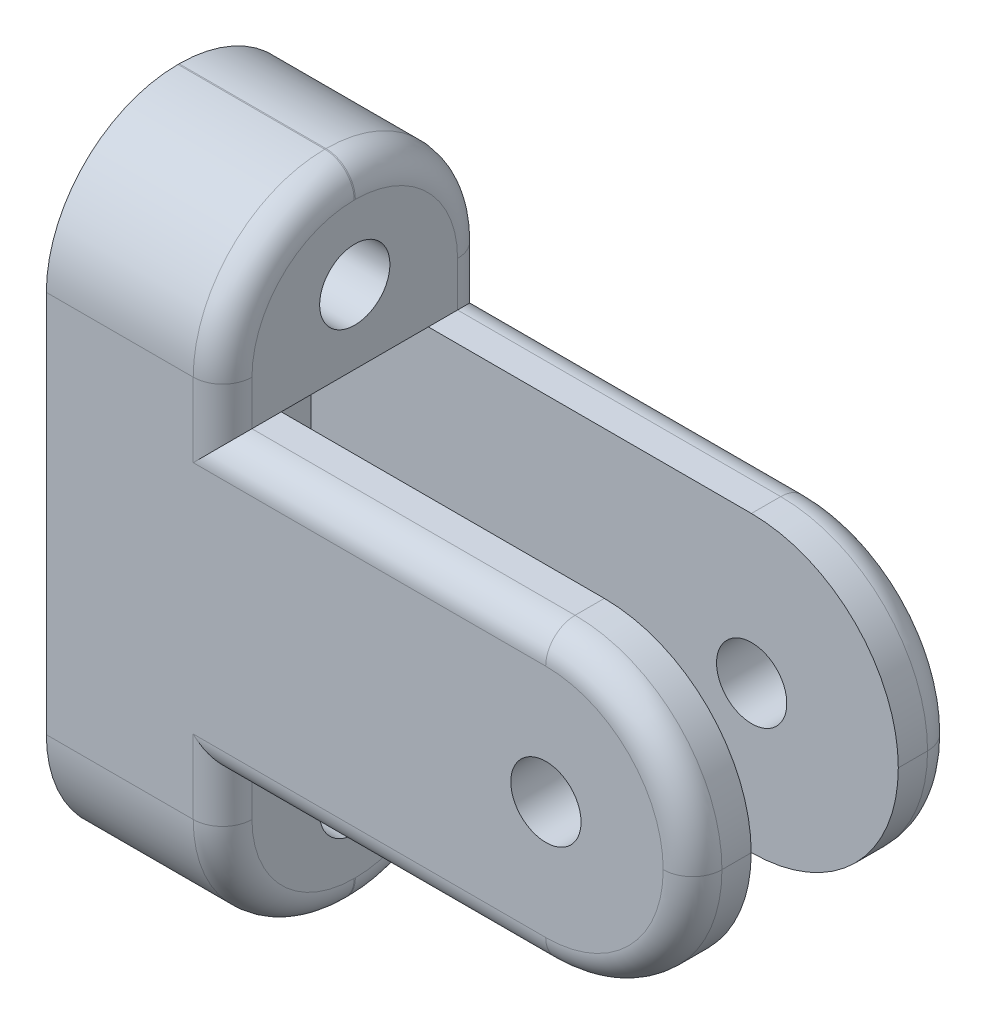
SolidWorks part; units mm, degrees
ref_plane "Front Plane" through (0, 0, 0) normal (0, 0, 1) x (1, 0, 0)
ref_plane "Top Plane" through (0, 0, 0) normal (0, 1, 0) x (1, 0, 0)
ref_plane "Right Plane" through (0, 0, 0) normal (1, 0, 0) x (0, 0, -1)
sketch "Sketch1" plane through (0, 0, 0) normal (1, 0, 0) x (0, 0, -1)
  line L1 (0, 0) -> (14.2875, 0)
  line L2 (0, 0) -> (0, 15.875)
  line L3 (0, 15.875) -> (14.2875, 15.875)
  line L4 (14.2875, 0) -> (14.2875, 15.875)
  dimension "D1" = 14.2875
  dimension "D2" = 15.875
extrude "Boss-Extrude1" add sketch "Sketch1" along normal blind 34.925
sketch "Sketch2" plane through (34.925, 0, 0) normal (1, 0, 0) x (0, 0, -1)
  line L0 (0, 15.875) -> (14.2875, 0) construction
  line L1 (14.2875, 0) -> (14.2875, 15.875) construction
  line L2 (0, 0) -> (14.2875, 0) construction
  line L4 (3.1687, 0) -> (11.1189, 0)
  line L5 (14.2875, 15.875) -> (0, 0) construction
  line L6 (3.1687, 0) -> (3.1687, 15.875)
  line L7 (3.1687, 15.875) -> (11.1189, 15.875)
  line L8 (11.1189, 0) -> (11.1189, 15.875)
  line L9 (3.1687, 0) -> (11.1189, 15.875) construction
  line L10 (3.1687, 15.875) -> (11.1189, 0) construction
  point P7 (7.1438, 7.9375)
  dimension "D1" = 15.875
  dimension "D2" = 7.9502
extrude "Cut-Extrude1" cut sketch "Sketch2" against normal blind 31.75
hole_wizard "#6 Clearance Hole1" positions "Sketch3" profile "Sketch4" hole size "#6" standard "ANSI Inch" end condition through all
sketch "Sketch3" plane through (0, 0, -14.2875) normal (0, 0, -1) x (-1, 0, 0)
  line L1 (-34.925, 7.9375) -> (0, 7.9375) construction
  line L2 (-34.925, 0) -> (-34.925, 15.875) construction
  line L3 (0, 0) -> (0, 15.875) construction
  point P0 (-27.0002, 7.9375)
  dimension "D1" = 27.0002
sketch "Sketch4" plane through (27.0002, 7.9375, -14.2875) normal (1, 0, 0) x (0, 1, 0)
  line L0 (0, 0) -> (0, 14.2875)
  line L1 (0, 14.2875) -> (1.8986, 14.2875)
  line L2 (1.8986, 14.2875) -> (1.8986, 0)
  line L5 (1.8986, 0) -> (0, 0)
  line L11 (0, -6.35) -> (0, 107.95) construction
  dimension "Thru Hole Dia." = 3.7973
  dimension "Thru Hole Depth" = 14.2875
sketch "Sketch5" plane through (0, 0, 0) normal (-1, 0, 0) x (0, 0, 1)
  line L0 (0, 15.875) -> (0, 0) construction
  line L1 (-14.2875, 15.875) -> (0, 15.875)
  line L2 (-14.2875, 15.875) -> (-14.2875, 25.4)
  line L3 (-14.2875, 25.4) -> (0, 25.4)
  line L4 (0, 15.875) -> (0, 25.4)
  line L5 (-14.2875, 0) -> (0, 0)
  line L6 (-14.2875, 0) -> (-14.2875, -9.525)
  line L7 (-14.2875, -9.525) -> (0, -9.525)
  line L8 (0, 0) -> (0, -9.525)
  line L9 (-14.2875, 0) -> (-14.2875, 15.875) construction
  dimension "D1" = 9.525
  dimension "D2" = 9.525
extrude "Boss-Extrude2" add sketch "Sketch5" against normal blind 9.525
hole_wizard "#6 Clearance Hole2" positions "Sketch6" profile "Sketch7" hole size "#6" standard "ANSI Inch" end condition through all
sketch "Sketch6" plane through (0, 0, 0) normal (-1, 0, 0) x (0, 0, 1)
  line L0 (-7.1438, 25.4) -> (-7.1437, -9.525) construction
  line L1 (0, 25.4) -> (-14.2875, 25.4) construction
  line L2 (-14.2875, -9.525) -> (0, -9.525) construction
  line L4 (0, 0) -> (-3.1687, 0) construction
  line L5 (-14.2875, 15.875) -> (-11.1189, 15.875) construction
  point P0 (-7.1438, 19.8438)
  point P2 (-7.1437, -3.9688)
  dimension "D1" = 3.9688
  dimension "D2" = 3.9688
sketch "Sketch7" plane through (0, 19.8438, -7.1438) normal (0, 1, 0) x (0, 0, 1)
  line L0 (0, 0) -> (0, 34.925)
  line L1 (0, 34.925) -> (1.8986, 34.925)
  line L2 (1.8986, 34.925) -> (1.8986, 0)
  line L5 (1.8986, 0) -> (0, 0)
  line L11 (0, -6.35) -> (0, 107.95) construction
  dimension "Thru Hole Dia." = 3.7973
  dimension "Thru Hole Depth" = 34.925
fillet "Fillet1" radius 7.112 4 edges at (4.7625, -9.525, 0) (4.7625, -9.525, -14.2875) (4.7625, 25.4, 0) (4.7625, 25.4, -14.2875)
fillet "Fillet3" radius 7.9375 4 edges at (34.925, 0, -1.5843) (34.925, 0, -12.7032) (34.925, 15.875, -12.7032) (34.925, 15.875, -1.5843)
fillet "Fillet2" radius 1.5875 18 edges at (9.525, -1.2065, 0) (9.525, -7.4419, -2.0831) (9.525, -9.525, -7.1437) (9.525, -7.4419, -12.2044) (9.525, 17.0815, 0) (9.525, 23.3169, -2.0831) (9.525, 25.4, -7.1437) (9.525, 23.3169, -12.2044) (18.2562, 0, 0) (18.2562, 0, -14.2875) (9.525, -1.2065, -14.2875) (18.2562, 15.875, 0) (9.525, 17.0815, -14.2875) (18.2562, 15.875, -14.2875) (32.6002, 2.3248, 0) (32.6002, 13.5502, 0) (32.6002, 2.3248, -14.2875) (32.6002, 13.5502, -14.2875)
